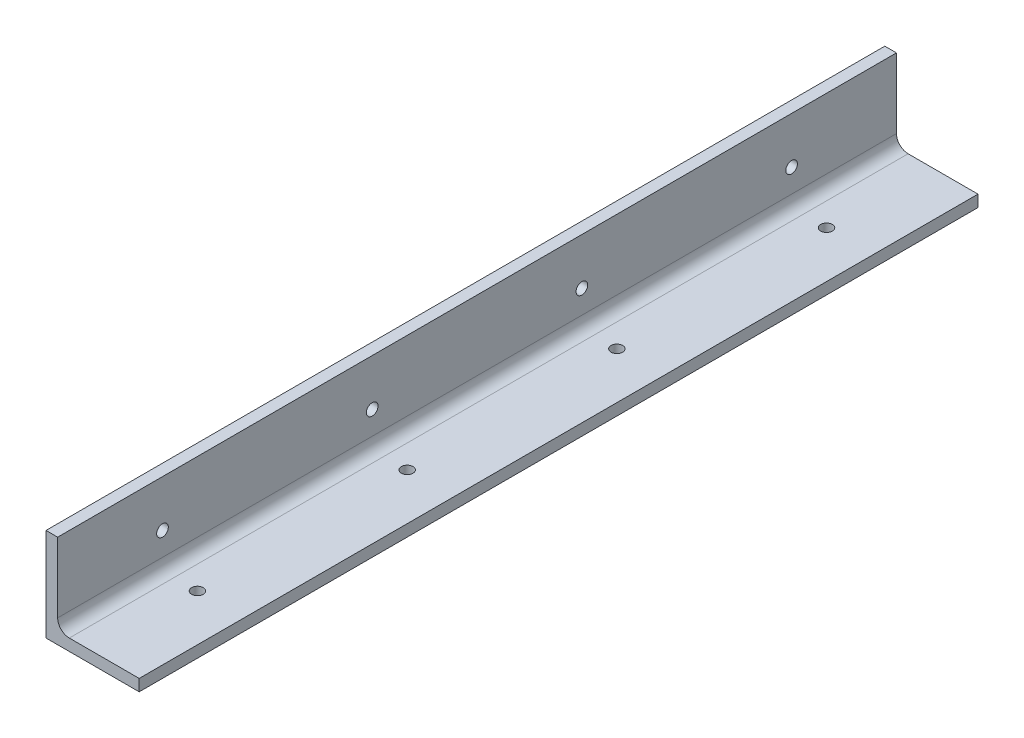
SolidWorks part; units mm, degrees
ref_plane "Front Plane" through (0, 0, 0) normal (0, 0, 1) x (1, 0, 0)
ref_plane "Top Plane" through (0, 0, 0) normal (0, 1, 0) x (1, 0, 0)
ref_plane "Right Plane" through (0, 0, 0) normal (1, 0, 0) x (0, 0, -1)
sketch "Sketch1" plane through (0, 0, 0) normal (0, 0, 1) x (1, 0, 0)
  line L1 (-29.6094, -21.0031) -> (21.1906, -21.0031)
  line L2 (-29.6094, -21.0031) -> (-29.6094, -27.3531)
  line L3 (-29.6094, -27.3531) -> (21.1906, -27.3531)
  line L4 (21.1906, -21.0031) -> (21.1906, -27.3531)
  line L5 (-29.6094, -21.0031) -> (-23.2594, -21.0031)
  line L6 (-29.6094, -21.0031) -> (-29.6094, 23.4469)
  line L7 (-29.6094, 23.4469) -> (-23.2594, 23.4469)
  line L8 (-23.2594, -21.0031) -> (-23.2594, 23.4469)
  dimension "D1" = 6.35
  dimension "D2" = 6.35
  dimension "D3" = 50.8
  dimension "D4" = 44.45
extrude "Boss-Extrude1" add sketch "Sketch1" along normal blind 457.2 contours L5 L8 L7 L6 | L1 L4 L3 L2
fillet "Fillet1" radius 6.35 1 edges at (-23.2594, -21.0031, 228.6)
sketch "Sketch2" plane through (0, -27.3531, 0) normal (0, -1, 0) x (1, 0, 0)
  line L0 (-29.6094, 457.2) -> (-29.6094, 0) construction
  line L2 (-29.6094, 457.2) -> (21.1906, 457.2) construction
  point P0 (-4.2094, 400.05)
  dimension "D1" = 25.4
  dimension "D2" = 57.15
hole_wizard "1/4 (0.25) Diameter Hole1" positions "Sketch2" profile "Sketch3" hole size "1/4" standard "ANSI Inch" end condition through all
sketch "Sketch3" plane through (-4.2094, -27.3531, 400.05) normal (1, 0, 0) x (0, 0, -1)
  line L0 (0, 0) -> (0, 50.8)
  line L1 (0, 50.8) -> (3.175, 50.8)
  line L2 (3.175, 50.8) -> (3.175, 0)
  line L5 (3.175, 0) -> (0, 0)
  line L11 (0, -6.35) -> (0, 107.95) construction
  dimension "Thru Hole Dia." = 6.35
  dimension "Thru Hole Depth" = 50.8
pattern_linear "LPattern1" count 4 spacing 114.3 along (0, 0, -1) of "1/4 (0.25) Diameter Hole1"
sketch "Sketch4" plane through (-29.6094, 0, 0) normal (-1, 0, 0) x (0, 0, 1)
  line L0 (457.2, -27.3531) -> (0, -27.3531) construction
  line L1 (457.2, -27.3531) -> (457.2, 23.4469) construction
  point P0 (400.05, -1.9531)
  point P5 (457.2, -1.9531)
  dimension "D1" = 25.4
  dimension "D2" = 57.15
hole_wizard "1/4 (0.25) Diameter Hole2" positions "Sketch4" profile "Sketch5" hole size "1/4" standard "ANSI Inch" end condition through all
sketch "Sketch5" plane through (-29.6094, -1.9531, 400.05) normal (0, 1, 0) x (0, 0, 1)
  line L0 (0, 0) -> (0, 50.8)
  line L1 (0, 50.8) -> (3.175, 50.8)
  line L2 (3.175, 50.8) -> (3.175, 0)
  line L5 (3.175, 0) -> (0, 0)
  line L11 (0, -6.35) -> (0, 107.95) construction
  dimension "Thru Hole Dia." = 6.35
  dimension "Thru Hole Depth" = 50.8
pattern_linear "LPattern2" count 4 spacing 114.3 along (0, 0, -1) of "1/4 (0.25) Diameter Hole2"
